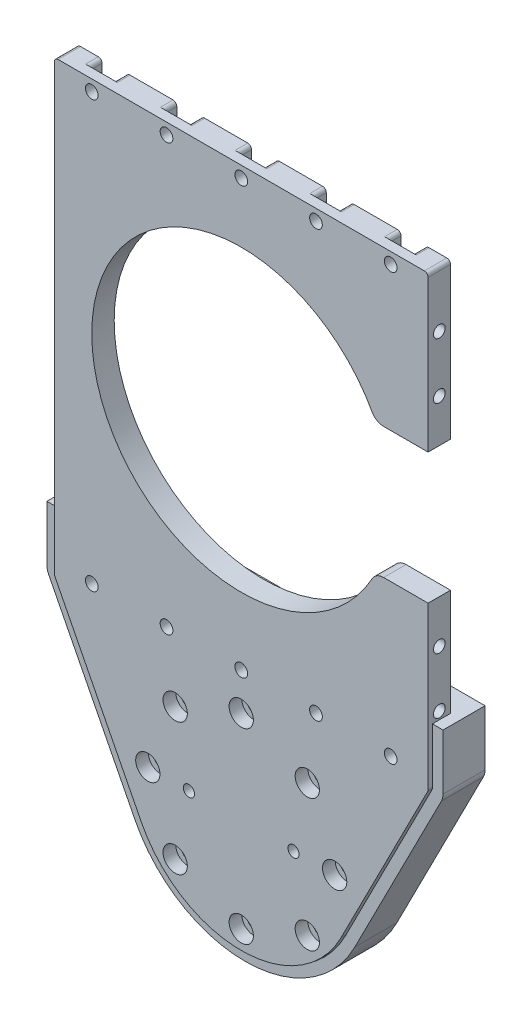
SolidWorks part; units mm, degrees
material "6061-T6 (SS)"
ref_plane "Front Plane" through (0, 0, 0) normal (0, 0, 1) x (1, 0, 0)
ref_plane "Top Plane" through (0, 0, 0) normal (0, 1, 0) x (1, 0, 0)
ref_plane "Right Plane" through (0, 0, 0) normal (1, 0, 0) x (0, 0, -1)
sketch "Sketch1" plane through (0, 0, 0) normal (0, 0, 1) x (1, 0, 0)
  line L0 (-30, 0) -> (-30, 152)
  line L1 (-30, 152) -> (30, 152)
  line L2 (30, 152) -> (30, 0)
  arc A0 (-30, 0) -> (30, 0) centre (0, 0) ccw
  dimension "D1" = 60
  dimension "D2" = 152
extrude "Boss-Extrude1" add sketch "Sketch1" along normal blind 6
sketch "Sketch7" plane through (0, 0, 6) normal (0, 0, 1) x (1, 0, 0)
  line L0 (-50, 32) -> (-26.7242, -13.6315)
  line L1 (30, 152) -> (50, 152)
  line L2 (30, 152) -> (30, 32)
  line L3 (30, 32) -> (50, 32) construction
  line L4 (50, 152) -> (50, 32)
  line L5 (-30, 152) -> (-50, 152)
  line L6 (-30, 152) -> (-30, 32)
  line L7 (-30, 32) -> (-50, 32) construction
  line L8 (-50, 152) -> (-50, 32)
  line L10 (26.7242, -13.6315) -> (50, 32)
  line L13 (30, 0) -> (30, 152)
  line L14 (30, 152) -> (-30, 152)
  line L15 (-30, 152) -> (-30, 0)
  line L16 (30, 0) -> (30, 152)
  line L17 (30, 152) -> (-30, 152)
  line L18 (-30, 152) -> (-30, 0)
  arc A1 (-30, 0) -> (30, 0) centre (0, 0) ccw
  arc A2 (-30, 0) -> (30, 0) centre (0, 0) ccw
  arc M9 (-30, 0) -> (30, 0) centre (0, 0) ccw
  line M10 (30, 0) -> (30, 152)
  line M12 (-30, 152) -> (-30, 0)
  dimension "D1" = 100
  dimension "D2" = 32
  dimension "D3" = 0
  dimension "D4" = 20
extrude "Boss-Extrude2" add sketch "Sketch7" against normal up to surface (6 mm away) contours L5 L8 L0 M9 M12 | L10 L4 L1 M9 M10 region at (-39.5172, 81.611, 6) region at (39.5172, 81.611, 6) up to face at (0, 68.5, 0)
sketch "Sketch2" plane through (0, 0, 6) normal (0, 0, 1) x (1, 0, 0)
  circle A0 centre (0, 0) radius 25
  point P6 (0, 25)
  point P12 (17.6777, 17.6777)
  point P13 (25, 0)
  point P14 (17.6777, -17.6777)
  point P15 (0, -25)
  point P16 (-17.6777, -17.6777)
  point P17 (-25, 0)
  point P18 (-17.6777, 17.6777)
  dimension "D1" = 50
  dimension "D2" = 8
hole_wizard "CBORE for M3 Hex Socket Head Cap Screw1" positions "Sketch2" profile "Sketch3" counterbore size "M3" standard "DIN" end condition through all
sketch "Sketch3" plane through (-17.6777, 17.6777, 6) normal (1, 0, 0) x (0, -1, 0)
  line L0 (0, 0) -> (0, 6)
  line L1 (0, 6) -> (1.7, 6)
  line L3 (1.7, 6) -> (1.7, 3.4)
  line L4 (1.7, 3.4) -> (3.25, 3.4)
  line L5 (3.25, 3.4) -> (3.25, 0)
  line L7 (3.25, 0) -> (0, 0)
  line L11 (0, -6.35) -> (0, 107.95) construction
  dimension "Thru Hole Dia." = 3.4
  dimension "Thru Hole Depth" = 6
  dimension "C'Bore Dia." = 6.5
  dimension "C'Bore Depth" = 3.4
sketch "Sketch4" plane through (0, 0, 0) normal (0, 0, -1) x (-1, 0, 0)
  line L0 (-50, 35) -> (50, 35) construction
  line L3 (-50, 152) -> (50, 152) construction
  line L4 (0, 152) -> (0, 149) construction
  line L8 (50, 32) -> (50, 152) construction
  line L9 (-50, 32) -> (-50, 152) construction
  point P7 (0, 35)
  point P23 (20, 35)
  point P24 (40, 35)
  point P25 (0, 35)
  point P26 (20, 35)
  point P27 (-20, 35)
  point P28 (0, 35)
  point P29 (-20, 35)
  point P30 (-40, 35)
  point P46 (0, 149)
  point P59 (20, 149)
  point P60 (40, 149)
  point P61 (0, 149)
  point P62 (20, 149)
  point P63 (-20, 149)
  point P64 (0, 149)
  point P65 (-20, 149)
  point P66 (-40, 149)
  dimension "D1" = 35
  dimension "D5" = 3
  dimension "D4" = 3
  dimension "D6" = 3
  dimension "D3" = 3
  dimension "D2" = 3
hole_wizard "CBORE for M3 Hex Socket Head Cap Screw2" positions "Sketch4" profile "Sketch6" counterbore size "M3" standard "DIN"
sketch "Sketch6" plane through (40, 149, 0) normal (1, 0, 0) x (0, 1, 0)
  line L0 (0, 0) -> (0, 11.0215)
  line L1 (0, 11.0215) -> (1.7, 10)
  line L2 (1.7, 10) -> (1.7, 3.4)
  line L3 (1.7, 3.4) -> (3.25, 3.4)
  line L4 (3.25, 3.4) -> (3.25, 0)
  line L5 (3.25, 0) -> (0, 0)
  line L10 (0, 11.0215) -> (-1.7, 10) construction
  line L11 (0, -6.35) -> (0, 107.95) construction
  dimension "Hole Dia." = 3.4
  dimension "Hole Depth" = 10
  dimension "C'Bore Dia." = 6.5
  dimension "C'Bore Depth" = 3.4
  dimension "Drill Angle" = 118
sketch "Sketch8" plane through (0, 0, 0) normal (0, 0, -1) x (-1, 0, 0)
  line L7 (50, 32) -> (50, 152) construction
  line L8 (-50, 110.5) -> (-35.9687, 110.5)
  line L9 (-50, 32) -> (-50, 152) construction
  line L11 (-35.9687, 75.5) -> (-50, 75.5)
  line L12 (-50, 75.5) -> (-50, 110.5)
  line L13 (-35.9687, 110.5) -> (-35.9687, 75.5) construction
  arc A0 (-35.9687, 75.5) -> (-35.9687, 110.5) centre (0, 93) ccw
  dimension "D2" = 93
  dimension "D3" = 80
  dimension "D1" = 50
  dimension "D4" = 35
extrude "Cut-Extrude1" cut sketch "Sketch8" against normal up to next and the other way through all
sketch "Sketch11" plane through (0, 0, 0) normal (0, 0, -1) x (-1, 0, 0)
  circle A0 centre (0, 0) radius 14
  point P6 (-14, 0)
  point P8 (14, 0)
  dimension "D1" = 28
hole_wizard "Ø3.0mm Dowel Hole1" positions "Sketch11" profile "Sketch10" hole size "Ø3.0" standard "BSI" end condition through all
sketch "Sketch10" plane through (-14, 0, 0) normal (1, 0, 0) x (0, 1, 0)
  line L0 (0, 0) -> (0, 6)
  line L1 (0, 6) -> (1.5, 6)
  line L2 (1.5, 6) -> (1.5, 0)
  line L5 (1.5, 0) -> (0, 0)
  line L11 (0, -6.35) -> (0, 107.95) construction
  dimension "Thru Hole Dia." = 3
  dimension "Thru Hole Depth" = 6
sketch "Sketch12" plane through (0, 0, 0) normal (0, 0, -1) x (-1, 0, 0)
  line L0 (-43.25, 149) -> (-43.25, 152)
  line L1 (-43.25, 152) -> (-36.75, 152)
  line L2 (-36.75, 152) -> (-36.75, 149)
  line L3 (-38.75, 152) -> (-21.25, 152) construction
  line L4 (-23.25, 149) -> (-23.25, 152)
  line L5 (-23.25, 152) -> (-16.75, 152)
  line L6 (-16.75, 152) -> (-16.75, 149)
  line L7 (-3.25, 149) -> (-3.25, 152)
  line L8 (-3.25, 152) -> (3.25, 152)
  line L9 (3.25, 152) -> (3.25, 149)
  line L10 (16.75, 149) -> (16.75, 152)
  line L11 (16.75, 152) -> (23.25, 152)
  line L12 (23.25, 152) -> (23.25, 149)
  line L13 (36.75, 149) -> (36.75, 152)
  line L14 (36.75, 152) -> (43.25, 152)
  line L15 (43.25, 152) -> (43.25, 149)
  arc A0 (-41.25, 152) -> (-38.75, 152) centre (-40, 149) ccw construction
  arc A1 (-41.25, 152) -> (-38.75, 152) centre (-40, 149) ccw construction
  arc A2 (-43.25, 149) -> (-36.75, 149) centre (-40, 149) ccw
  arc A5 (-23.25, 149) -> (-16.75, 149) centre (-20, 149) ccw
  arc A6 (-3.25, 149) -> (3.25, 149) centre (0, 149) ccw
  arc A7 (16.75, 149) -> (23.25, 149) centre (20, 149) ccw
  arc A8 (36.75, 149) -> (43.25, 149) centre (40, 149) ccw
  dimension "D1" = 5
extrude "Cut-Extrude2" cut sketch "Sketch12" against normal up to surface (3.4 mm away) and the other way through all up to face at (38.3, 149, 3.4)
fillet "Fillet3" radius 1 14 edges at (23.25, 152, 1.7) (16.75, 152, 1.7) (3.25, 152, 1.7) (-3.25, 152, 1.7) (-16.75, 152, 1.7) (-23.25, 152, 1.7) (-36.75, 152, 1.7) (-43.25, 152, 1.7) (-50, 152, 3) (-50, 32, 3) (50, 32, 3) (50, 152, 3) (36.75, 152, 1.7) (43.25, 152, 1.7)
sketch "Sketch15" plane through (50, 0, 0) normal (1, 0, 0) x (0, 0, -1)
  line L0 (-3, 110.5) -> (-3, 75.5) construction
  line L2 (-6, 75.5) -> (-3, 75.5) construction
  line L4 (-6, 110.5) -> (19.2728, 110.5) construction
  line L5 (-6, 151) -> (-6, 110.5) construction
  line L6 (0, 110.5) -> (-6, 110.5) construction
  line L8 (-3, 93) -> (37.8118, 93) construction
  point P7 (-3, 137)
  point P9 (-3, 122)
  point P36 (-3, 64)
  point P37 (-3, 49)
  dimension "D2" = 15
hole_wizard "Tap Drill for M3 Helicoil1" positions "Sketch15" profile "Sketch14" hole size "M3x0.5" standard "DIN"
sketch "Sketch14" plane through (50, 137, 3) normal (0, 1, 0) x (0, 0, -1)
  line L0 (0, 0) -> (0, 15.9464)
  line L1 (0, 15.9464) -> (1.575, 15)
  line L2 (1.575, 15) -> (1.575, 0)
  line L5 (1.575, 0) -> (0, 0)
  line L10 (0, 15.9464) -> (-1.575, 15) construction
  line L11 (0, -6.35) -> (0, 107.95) construction
  dimension "Hole Dia." = 3.15
  dimension "Hole Depth" = 15
  dimension "Drill Angle" = 118
fillet "Fillet4" radius 3.5 2 edges at (35.9687, 75.5, 3) (35.9687, 110.5, 3)
sketch "Sketch17" plane through (0, 0, 0) normal (0, 0, -1) x (-1, 0, 0)
  line L0 (-50, 44.1031) -> (50, 44.1031) construction
  line L1 (-50, 32.2403) -> (-50, 75.5) construction
  line L2 (50, 32.2403) -> (50, 151) construction
  line L3 (50, 44.1031) -> (50, 32.2403) construction
  line L5 (-50, 32.2403) -> (-50, 44.1031) construction
  line L6 (-49.8908, 31.7859) -> (-26.7242, -13.6315) construction
  line L7 (26.7242, -13.6315) -> (49.8908, 31.7859) construction
  line L8 (-49.8908, 31.7859) -> (-26.7242, -13.6315) construction
  line L9 (26.7242, -13.6315) -> (49.8908, 31.7859) construction
  line L10 (29.3966, -14.9947) -> (52.5632, 30.4228)
  line L11 (53, 47.1031) -> (53, 32.2403)
  line L12 (-53, 47.1031) -> (53, 47.1031)
  line L13 (-53, 32.2403) -> (-53, 47.1031)
  line L14 (-52.5632, 30.4228) -> (-29.3966, -14.9947)
  line L15 (26.8578, -13.6997) -> (50.0244, 31.7178)
  line L16 (50.15, 44.2531) -> (50.15, 32.2403)
  line L17 (-50.15, 44.2531) -> (50.15, 44.2531)
  line L18 (-50.15, 32.2403) -> (-50.15, 44.2531)
  line L19 (-50.0244, 31.7178) -> (-26.8578, -13.6997)
  arc A0 (-26.7242, -13.6315) -> (26.7242, -13.6315) centre (0, 0) ccw construction
  arc A1 (-50, 32.2403) -> (-49.8908, 31.7859) centre (-49, 32.2403) ccw construction
  arc A2 (49.8908, 31.7859) -> (50, 32.2403) centre (49, 32.2403) ccw construction
  arc A3 (-26.7242, -13.6315) -> (26.7242, -13.6315) centre (0, 0) ccw construction
  arc A4 (-50, 32.2403) -> (-49.8908, 31.7859) centre (-49, 32.2403) ccw construction
  arc A5 (49.8908, 31.7859) -> (50, 32.2403) centre (49, 32.2403) ccw construction
  arc A6 (-29.3966, -14.9947) -> (29.3966, -14.9947) centre (0, 0) ccw
  arc A7 (52.5632, 30.4228) -> (53, 32.2403) centre (49, 32.2403) ccw
  arc A8 (-53, 32.2403) -> (-52.5632, 30.4228) centre (-49, 32.2403) ccw
  arc A9 (-26.8578, -13.6997) -> (26.8578, -13.6997) centre (0, 0) ccw
  arc A10 (50.0244, 31.7178) -> (50.15, 32.2403) centre (49, 32.2403) ccw
  arc A11 (-50.15, 32.2403) -> (-50.0244, 31.7178) centre (-49, 32.2403) ccw
  point P6 (50, 32.2403)
  dimension "D1" = 3
  dimension "D2" = 0.15
extrude "Boss-Extrude3" add sketch "Sketch17" against normal blind 5 separate body
sketch "Sketch18" plane through (0, 0, 0) normal (0, 0, -1) x (-1, 0, 0)
  line L5 (29.3966, -14.9947) -> (52.5632, 30.4228)
  line L6 (53, 32.2403) -> (53, 47.1031)
  line L7 (53, 47.1031) -> (-53, 47.1031)
  line L8 (-53, 47.1031) -> (-53, 32.2403)
  line L9 (-52.5632, 30.4228) -> (-29.3966, -14.9947)
  line L10 (29.3966, -14.9947) -> (52.5632, 30.4228)
  line L11 (53, 32.2403) -> (53, 47.1031)
  line L12 (53, 47.1031) -> (-53, 47.1031)
  line L13 (-53, 47.1031) -> (-53, 32.2403)
  line L14 (-52.5632, 30.4228) -> (-29.3966, -14.9947)
  arc A3 (-29.3966, -14.9947) -> (29.3966, -14.9947) centre (0, 0) ccw
  arc A4 (52.5632, 30.4228) -> (53, 32.2403) centre (49, 32.2403) ccw
  arc A5 (-53, 32.2403) -> (-52.5632, 30.4228) centre (-49, 32.2403) ccw
  arc A6 (-29.3966, -14.9947) -> (29.3966, -14.9947) centre (0, 0) ccw
  arc A7 (52.5632, 30.4228) -> (53, 32.2403) centre (49, 32.2403) ccw
  arc A8 (-53, 32.2403) -> (-52.5632, 30.4228) centre (-49, 32.2403) ccw
  dimension "D1" = 0
extrude "Boss-Extrude4" add sketch "Sketch18" along normal blind 6.25
sketch "Sketch19" plane through (0, 0, 0) normal (0, 0, 1) x (1, 0, 0)
  point P0 (-40, 35)
  point P3 (-20, 35)
  point P6 (0, 35)
  point P9 (20, 35)
  point P12 (40, 35)
  point P15 (0, 25)
  point P18 (17.6777, 17.6777)
  point P21 (-17.6777, 17.6777)
  point P24 (-25, 0)
  point P27 (-17.6777, -17.6777)
  point P30 (0, -25)
  point P33 (17.6777, -17.6777)
  point P36 (25, 0)
  point P39 (14, 0)
  point P42 (-14, 0)
hole_wizard "Ø6.0 mm Dowel Holes1" positions "Sketch19" profile "Sketch20" hole size "Ø6.0" standard "DIN" end condition through all
sketch "Sketch20" plane through (-40, 35, 0) normal (1, 0, 0) x (0, -1, 0)
  line L0 (0, 0) -> (0, 6.25)
  line L1 (0, 6.25) -> (3, 6.25)
  line L2 (3, 6.25) -> (3, 0)
  line L5 (3, 0) -> (0, 0)
  line L11 (0, -6.35) -> (0, 107.95) construction
  dimension "Thru Hole Dia." = 6
  dimension "Thru Hole Depth" = 6.25
sketch "Sketch22" plane through (0, 0, 0) normal (0, 0, 1) x (1, 0, 0)
  line L0 (50.15, 44.2531) -> (50.15, 32.2403) construction
  line L1 (-50.15, 44.2531) -> (50.15, 44.2531)
  line L2 (-50.15, 44.2531) -> (-50.15, 50.9106)
  line L3 (-50.15, 50.9106) -> (50.15, 50.9106)
  line L4 (50.15, 44.2531) -> (50.15, 50.9106)
extrude "Cut-Extrude3" cut sketch "Sketch22" along normal blind 6
